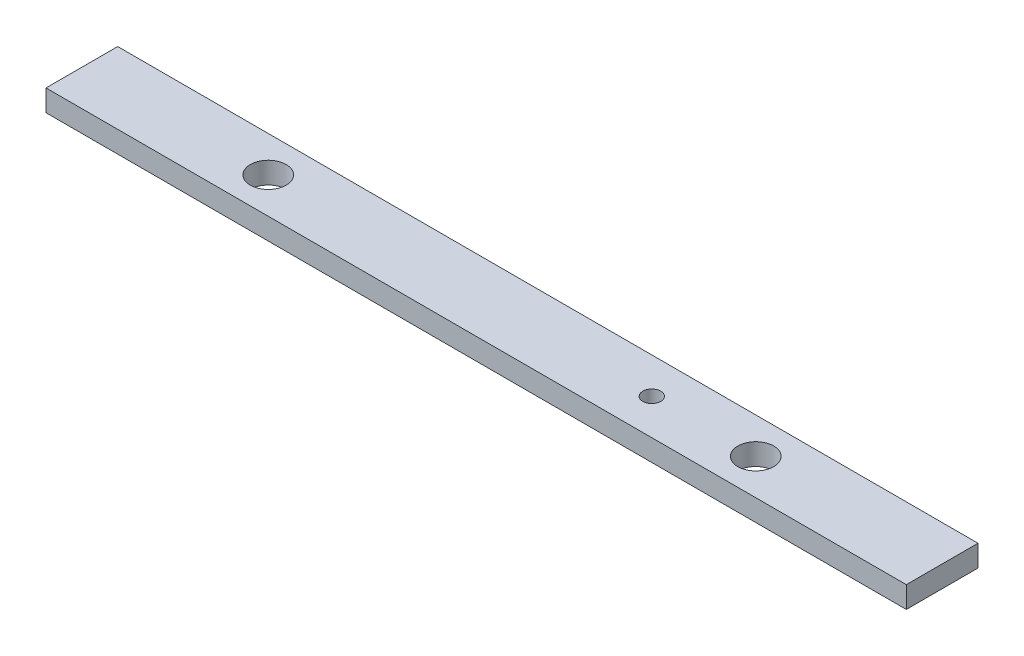
SolidWorks part; units mm, degrees
ref_plane "Front Plane" through (0, 0, 0) normal (0, 0, 1) x (1, 0, 0)
ref_plane "Top Plane" through (0, 0, 0) normal (0, 1, 0) x (1, 0, 0)
ref_plane "Right Plane" through (0, 0, 0) normal (1, 0, 0) x (0, 0, -1)
sketch "Sketch3" plane through (0, 0, 0) normal (0, 1, 0) x (1, 0, 0)
  line L1 (-60, -5) -> (60, -5)
  line L2 (-60, -5) -> (-60, 5)
  line L3 (-60, 5) -> (60, 5)
  line L4 (60, -5) -> (60, 5)
  line L5 (-60, -5) -> (60, 5) construction
  line L6 (-60, 5) -> (60, -5) construction
  point P0 (0, 0)
  dimension "D1" = 120
  dimension "D2" = 10
extrude "Boss-Extrude1" add sketch "Sketch3" along normal blind 3
sketch "Sketch5" plane through (0, 0, 0) normal (0, 1, 0) x (1, 0, 0)
  line L0 (-64.2904, 0) -> (64.0944, 0) construction
  line L1 (0, 30.7056) -> (0, -26.5382) construction
  circle A0 centre (-34, 0) radius 2.5
  circle A1 centre (34, 0) radius 2.5
  circle A3 centre (19.5, 0) radius 1.25
  point P12 (0, 0)
  point P13 (-10.4444, 0)
  point P14 (7.3089, 0)
  dimension "D1" = 5
  dimension "D3" = 2.5
  dimension "D2" = 34
  dimension "D4" = 19.5
extrude "Cut-Extrude1" cut sketch "Sketch5" along normal up to surface (3 mm away) up to face at (0, 3, 0)
sketch "Sketch6" plane through (0, 0, 0) normal (0, 1, 0) x (1, 0, 0)
  line L0 (-60, 0) -> (60, 0) construction
  line L1 (-60, 5) -> (-60, -5) construction
  line L2 (60, -5) -> (60, 5) construction
ref_axis "Axis1" through (-60, 0, 0) along (1, 0, 0)
